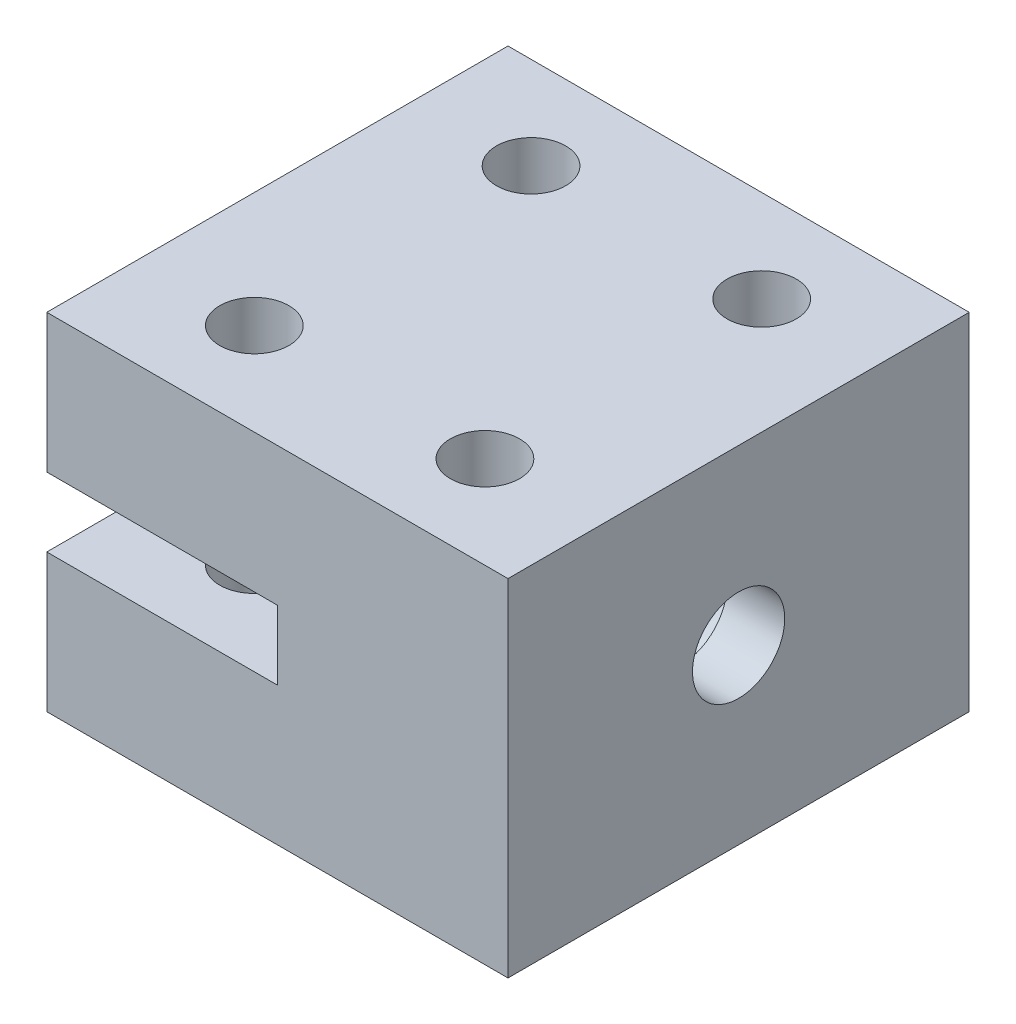
SolidWorks part; units mm, degrees
ref_plane "Front Plane" through (0, 0, 0) normal (0, 0, 1) x (1, 0, 0)
ref_plane "Top Plane" through (0, 0, 0) normal (0, 1, 0) x (1, 0, 0)
ref_plane "Right Plane" through (0, 0, 0) normal (1, 0, 0) x (0, 0, -1)
sketch "Sketch1" plane through (0, 0, 0) normal (0, 1, 0) x (1, 0, 0)
  line L5 (-10, 10) -> (10, 10)
  line L6 (-10, 10) -> (-10, -10)
  line L7 (-10, -10) -> (10, -10)
  line L8 (10, 10) -> (10, -10)
  line L9 (-10, 10) -> (10, -10) construction
  line L10 (-10, -10) -> (10, 10) construction
  point P1 (0, 0)
  dimension "D1" = 20
  dimension "D2" = 20
extrude "Boss-Extrude1" add sketch "Sketch1" along normal mid plane 15
extrude "Cut-Extrude2" cut sketch "Sketch1<3>" against normal mid plane 3
sketch "Sketch1<3>" plane through (0, 0, 0) normal (0, 1, 0) x (1, 0, 0) same geometry as "Sketch1"
sketch "Sketch3" plane through (0, 0, 0) normal (0, 1, 0) x (1, 0, 0)
  line L0 (10, 10) -> (-10, 10) construction
  line L1 (0, 10) -> (10, 10)
  line L2 (0, 10) -> (0, -10)
  line L3 (0, -10) -> (10, -10)
  line L4 (10, 10) -> (10, -10)
extrude "Boss-Extrude2" add sketch "Sketch3" along normal mid plane 3
sketch "Sketch4" plane through (10, 0, 0) normal (1, 0, 0) x (0, 0, -1)
  circle A0 centre (0, 0) radius 2
  dimension "D1" = 4
extrude "Cut-Extrude3" cut sketch "Sketch4" against normal blind 5
sketch "Sketch5" plane through (0, 0, 0) normal (0, 1, 0) x (1, 0, 0)
  line L1 (-5, 6) -> (5, 6) construction
  line L2 (-5, 6) -> (-5, -6) construction
  line L3 (-5, -6) -> (5, -6) construction
  line L4 (5, 6) -> (5, -6) construction
  line L5 (-5, 6) -> (5, -6) construction
  line L6 (-5, -6) -> (5, 6) construction
  circle A0 centre (-5, 6) radius 1.5
  circle A1 centre (5, 6) radius 1.5
  circle A2 centre (5, -6) radius 1.5
  circle A3 centre (-5, -6) radius 1.5
  point P0 (0, 0)
  dimension "D3" = 3
  dimension "D1" = 10
  dimension "D2" = 12
extrude "mounthole" cut sketch "Sketch5" against normal through all both and the other way through all
fillet "Fillet1" [suppressed] radius 1
ref_plane "Plane1" through (5, 0, 0) normal (1, 0, 0) x (0, 0, -1)
sketch "Sketch6" plane through (5, 0, 0) normal (1, 0, 0) x (0, 0, -1)
  circle A0 centre (0, 0) radius 3.5
  dimension "D1" = 7
extrude "bearinghole" cut sketch "Sketch6" along normal blind 2.5
